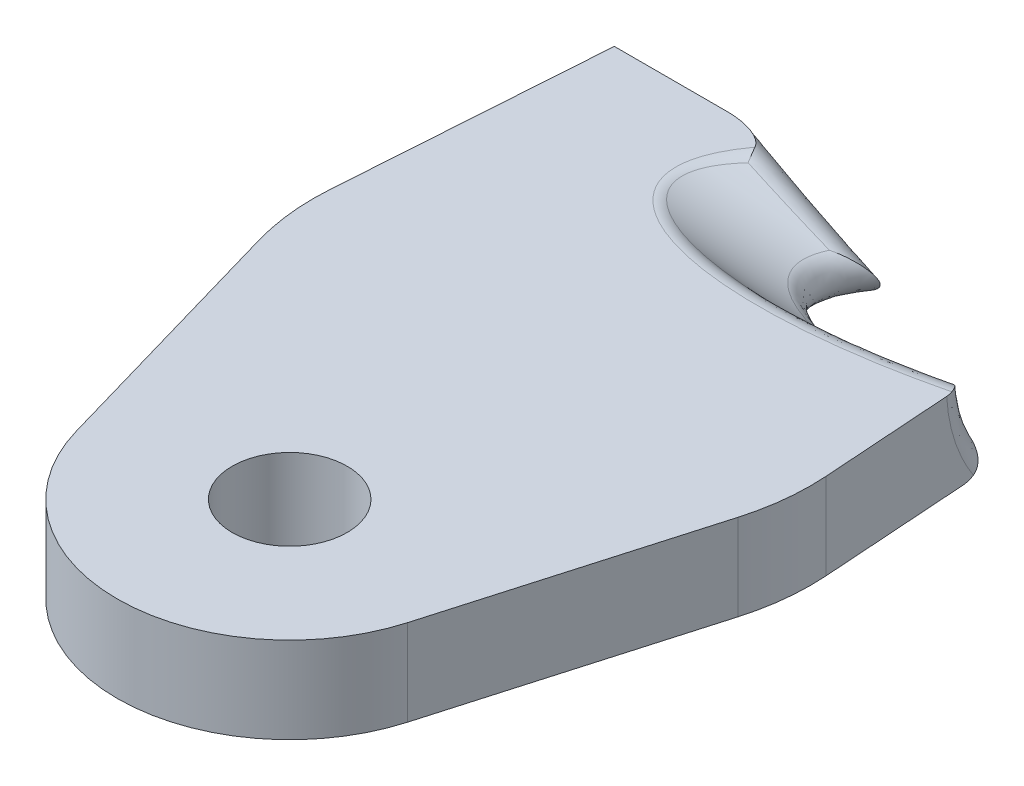
SolidWorks part; units mm, degrees
ref_plane "Front Plane" through (0, 0, 0) normal (0, 0, 1) x (1, 0, 0)
ref_plane "Top Plane" through (0, 0, 0) normal (0, 1, 0) x (1, 0, 0)
ref_plane "Right Plane" through (0, 0, 0) normal (1, 0, 0) x (0, 0, -1)
sketch3d "3DSketch2"
  line L2 (-343.3567, 9.525, 187.6335) -> (0, 9.525, 54.4858) construction
  line L6 (130.6288, -47.294, -40.389) -> (-395.8937, 181.725, 122.406) construction
  line L10 (0, 9.525, 571.6615) -> (-395.8937, 9.525, 122.406) construction
  line L11 (0, 9.525, 571.6615) -> (0, 9.525, 0) construction
sketch "Sketch1" plane through (0, 0, 0) normal (0, 1, 0) x (1, 0, 0)
  line L0 (27.718, -27.1226) -> (25.4, 6.7707)
  line L1 (25.4, 6.7707) -> (-25.4, 6.7707)
  line L4 (18.304, -59.7647) -> (27.718, -27.1226)
  line L6 (0, -54.4858) -> (0, 0) construction
  line L7 (-18.304, -59.7647) -> (-27.718, -27.1226)
  line L8 (-27.718, -27.1226) -> (-25.4, 6.7707)
  line L9 (18.304, -59.7647) -> (25.4, 6.7707) construction
  line L10 (-25.4, 6.7707) -> (-18.304, -59.7647) construction
  arc A0 (-18.304, -59.7647) -> (18.304, -59.7647) centre (0, -54.4858) ccw
  circle A1 centre (0, -54.4858) radius 6.35
  point P8 (0, 6.7707)
  point P11 (21.8983, 6.7707)
  dimension "D1" = 12.7
  dimension "D2" = 12.7
  dimension "D3" = 10
  dimension "D4" = 10
  dimension "D5" = 50.8
extrude "Boss-Extrude1" add sketch "Sketch1" against normal blind 9.525
ref_plane "Plane4" through (0, 9.525, 0) normal (-0.8822, 0.3837, 0.2728) x (0.2501, -0.1088, 0.9621)
sketch "Sketch2" plane through (0, 9.525, 0) normal (-0.8822, 0.3837, 0.2728) x (0.2501, -0.1088, 0.9621)
  circle A0 centre (0, 0) radius 12.7
  dimension "D1" = 25.4
extrude "Cut-Extrude2" cut sketch "Sketch2" along normal through all both and the other way through all
fillet "Fillet1" radius 2.54 4 edges at (3.0636, -4.8854, -6.7707) (14.9027, -9.525, -0.4832) (-4.8499, 0, 7.3447) (26.1649, -4.9926, 4.4129)
fillet "Fillet4" radius 25.4 2 edges at (-27.718, -4.7625, 27.1226) (27.718, -4.7625, 27.1226)
equation "\"D1@EdgeBend1\"=.125*1.5"
equation "\"D2@Sketch1\"=\"D1@Sketch1\""
equation "\"D4@Sketch1\"=\"D3@Sketch1\""
